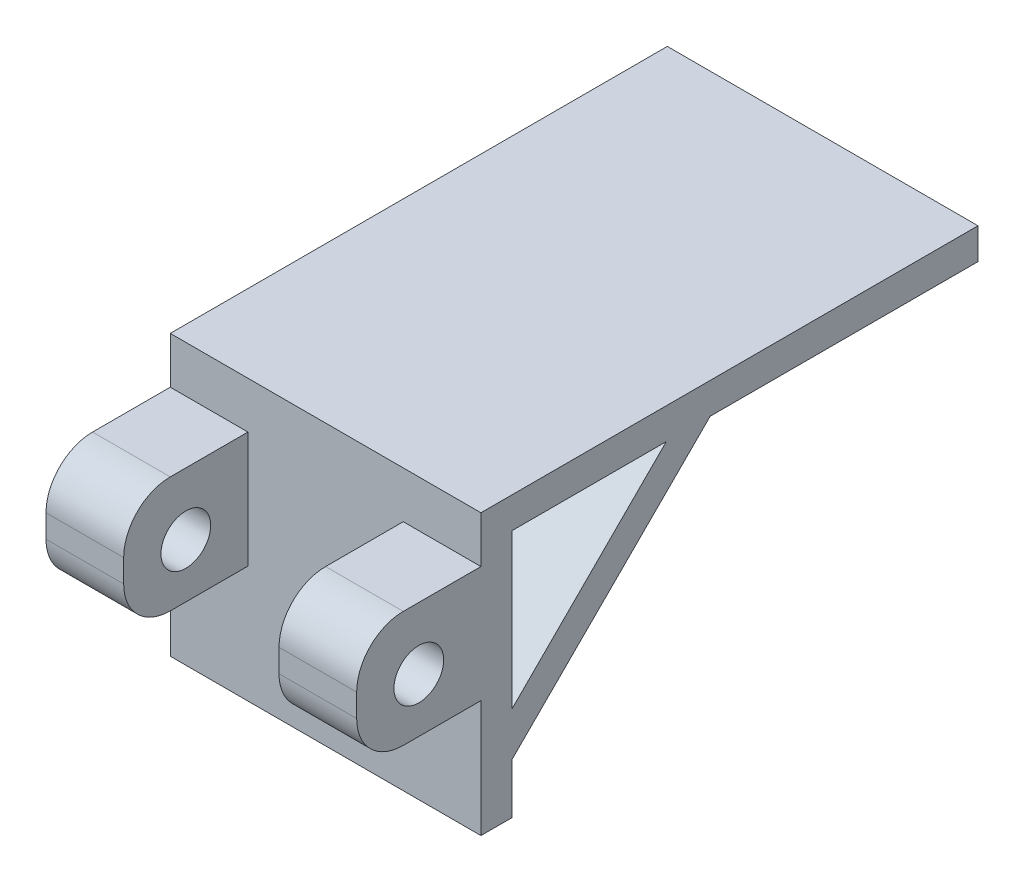
SolidWorks part; units mm, degrees
ref_plane "Front Plane" through (0, 0, 0) normal (0, 0, 1) x (1, 0, 0)
ref_plane "Top Plane" through (0, 0, 0) normal (0, 1, 0) x (1, 0, 0)
ref_plane "Right Plane" through (0, 0, 0) normal (1, 0, 0) x (0, 0, -1)
sketch "Sketch1" plane through (0, 0, 0) normal (0, 0, 1) x (1, 0, 0)
  line L0 (0, 0) -> (0, 7.5) construction
  line L1 (-10, -7.5) -> (10, -7.5)
  line L2 (-10, -7.5) -> (-10, 7.5)
  line L3 (-10, 7.5) -> (10, 7.5)
  line L4 (10, -7.5) -> (10, 7.5)
  line L5 (-10, -7.5) -> (10, 7.5) construction
  line L6 (-10, 7.5) -> (10, -7.5) construction
  line L7 (-5, 7.5) -> (5, 7.5)
  line L8 (-5, 7.5) -> (-5, 0)
  line L9 (-5, 0) -> (5, 0)
  line L10 (5, 7.5) -> (5, 0)
  point P0 (0, 0)
  dimension "D1" = 15
  dimension "D2" = 10
  dimension "D3" = 20
extrude "Boss-Extrude1" add sketch "Sketch1" along normal blind 8 contours L3 L10 L9 L8 L2 L1 L4 region at (0, -1.25, 0)
extrude "Boss-Extrude2" add sketch "Sketch1<3>" against normal blind 2 contours L3 L10 L9 L8 L2 L1 L4 | L10 L3 L8 L9 region at (0, -1.25, 0) region at (0, 3.75, 0)
sketch "Sketch1<3>" plane through (0, 0, 0) normal (0, 0, 1) x (1, 0, 0) same geometry as "Sketch1"
sketch "Sketch2" plane through (10, 0, 0) normal (1, 0, 0) x (0, 0, -1)
  line L0 (-8, 7.5) -> (0, 7.5) construction
  line L1 (-8, 7.5) -> (0, 7.5)
  line L2 (0, 7.5) -> (0, -15) construction
  circle A0 centre (-4, 3.5) radius 1.6
  dimension "D1" = 3.2
  dimension "D2" = 4
  dimension "D3" = 4
extrude "Cut-Extrude1" cut sketch "Sketch2" against normal through all contours A0 region at (10, 3.5, 4)
sketch "Sketch3" plane through (0, 0, 8) normal (0, 0, 1) x (1, 0, 0)
  line L0 (10, 0.0263) -> (-10, 0.0263)
  line L2 (-10, -7.5) -> (-10, 7.5) construction
  line L3 (10, -7.5) -> (10, 7.5) construction
  line L8 (10, 7.5) -> (5, 7.5)
  line L9 (5, 7.5) -> (5, 0)
  line L11 (-5, 0) -> (-5, 7.5)
  line L14 (-10, -7.5) -> (10, -7.5)
  line L15 (5, 0) -> (-5, 0)
  line L16 (10, 7.5) -> (5, 7.5) construction
  line L17 (5, 0.0263) -> (5, 0)
  line L19 (-5, 0) -> (-5, 0.0263)
  line L22 (-10, -7.5) -> (10, -7.5)
  line L24 (5, 0) -> (-5, 0)
  line L25 (-5, 7.5) -> (-10, 7.5)
  line L26 (-5, 7.5) -> (-10, 7.5)
  line L27 (-10, 7.5) -> (-10, -7.5)
  line L28 (-10, 7.5) -> (-10, -7.5)
  line L29 (10, -7.5) -> (10, 7.5)
  line L30 (10, -7.5) -> (10, 7.5)
  line M11 (5, 7.5) -> (5, 0)
  line M12 (5, 0) -> (-5, 0)
  line M13 (-5, 0) -> (-5, 7.5)
  line M15 (-10, 7.5) -> (-10, -7.5)
  line M16 (-10, -7.5) -> (10, -7.5)
  line M17 (10, -7.5) -> (10, 7.5)
  dimension "D1" = 0
extrude "Cut-Extrude3" cut sketch "Sketch3" against normal up to surface (8 mm away) contours L0 M17 M11 M12 M13 M15 M16 region at (0, -3.7434, 8) up to face at (0, 3.75, 0)
fillet "Fillet1" radius 3 4 edges at (-7.5, 0.0263, 8) (-7.5, 7.5, 8) (7.5, 7.5, 8) (7.5, 0.0263, 8)
sketch "Sketch4" plane through (0, 7.5, 0) normal (0, 1, 0) x (1, 0, 0)
  line L0 (-5, 0) -> (5, 0) construction
  line L1 (-10, -5) -> (-10, 2) construction
  line L2 (10, -5) -> (10, 2) construction
  line L3 (-10, 2) -> (10, 2) construction
  line L4 (-5, 0) -> (5, 0)
  line L5 (-10, 0) -> (-10, 2)
  line L6 (10, 0) -> (10, 2)
  line L7 (-10, 2) -> (10, 2)
  line L8 (5, 0) -> (10, 0)
  line L9 (-5, 0) -> (-10, 0)
extrude "Boss-Extrude3" add sketch "Sketch4" along normal blind 3
sketch "Sketch5" plane through (0, 0, -2) normal (0, 0, -1) x (-1, 0, 0)
  line L0 (-10, 10.5) -> (10, 10.5) construction
  line L1 (-10, 10.5) -> (10, 10.5)
  line L2 (-10, 10.5) -> (-10, 8.5)
  line L3 (-10, -7.5) -> (-10, 10.5) construction
  line L4 (-10, 8.5) -> (10, 8.5)
  line L5 (10, -7.5) -> (10, 10.5) construction
  line L6 (10, 8.5) -> (10, 10.5)
  dimension "D1" = 2
extrude "Boss-Extrude4" add sketch "Sketch5" along normal blind 30
sketch "Sketch8" plane through (10, 0, 0) normal (1, 0, 0) x (0, 0, -1)
  line L0 (14.7571, 8.5) -> (11.9346, 8.5)
  line L1 (32, 8.5) -> (2, 8.5) construction
  line L2 (11.9346, 8.5) -> (2, -1.4346)
  line L3 (2, -7.5) -> (2, 8.5) construction
  line L4 (2, -1.4346) -> (2, -4.2571)
  line L5 (2, -4.2571) -> (14.7571, 8.5)
  dimension "D1" = 1.9958
extrude "Boss-Extrude5" add sketch "Sketch8" against normal up to surface (20 mm away) up to face at (-10, 3.7982, -3.3964)
